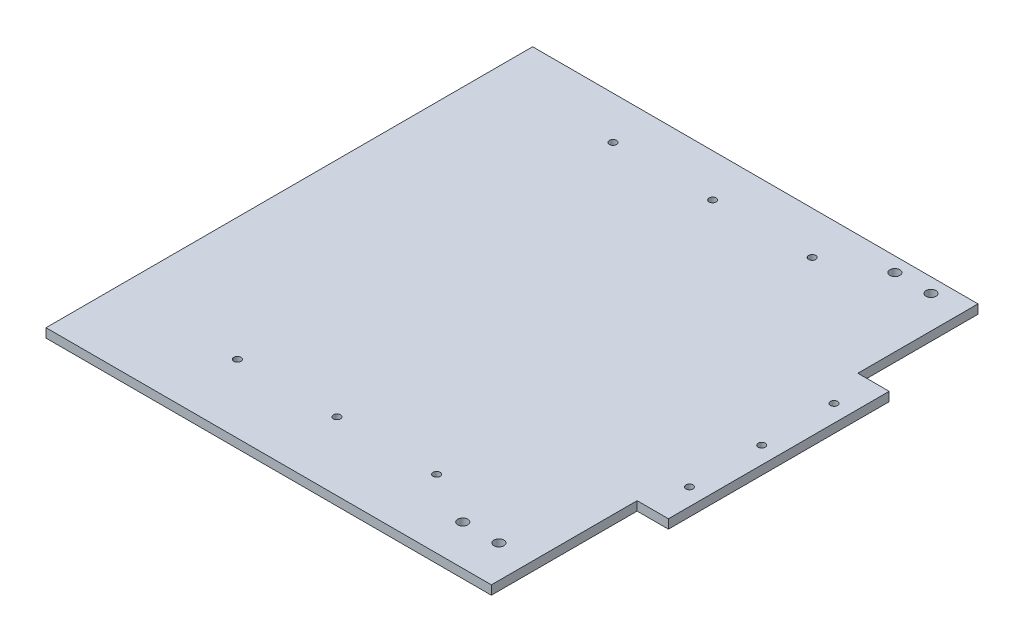
SolidWorks part; units mm, degrees
material "Cedar"
ref_plane "Front Plane" through (0, 0, 0) normal (0, 0, 1) x (1, 0, 0)
ref_plane "Top Plane" through (0, 0, 0) normal (0, 1, 0) x (1, 0, 0)
ref_plane "Right Plane" through (0, 0, 0) normal (1, 0, 0) x (0, 0, -1)
sketch "Sketch1" plane through (0, 0, 0) normal (0, 1, 0) x (1, 0, 0)
  line L0 (72.8376, -16.2766) -> (72.8376, -52.4668) construction
  line L1 (-156.5, -171) -> (156.5, -171)
  line L2 (-156.5, -171) -> (-156.5, 171)
  line L3 (-156.5, 171) -> (156.5, 171)
  line L4 (156.5, -171) -> (156.5, 171)
  line L5 (-156.5, -171) -> (156.5, 171) construction
  line L6 (-156.5, 171) -> (156.5, -171) construction
  point P0 (0, 0)
  dimension "D1" = 342
  dimension "D2" = 313
extrude "Boss-Extrude1" add sketch "Sketch1" against normal blind 6.35
ref_plane "Plane1" through (0, 0, -9) normal (0, 0, -1) x (-1, 0, 0)
sketch "Sketch3" plane through (0, 0, 0) normal (0, 1, 0) x (1, 0, 0)
  line L0 (156.5, 9) -> (-156.5, 9) construction
  line L1 (156.5, -171) -> (156.5, 171) construction
  line L2 (-156.5, 171) -> (-156.5, -171) construction
  line L3 (55, 9) -> (-55, 9) construction
  line L4 (156.5, 86.5702) -> (156.5, -68.5702)
  line L5 (156.5, -68.5702) -> (178.5, -68.5702)
  line L6 (178.5, -68.5702) -> (178.5, 86.5702)
  line L7 (178.5, 86.5702) -> (156.5, 86.5702)
  line L8 (166.5, 59.8) -> (166.5, 9) construction
  circle A0 centre (166.5, 9) radius 2.5
  circle A1 centre (166.5, -41.8) radius 2.5
  circle A2 centre (166.5, 59.8) radius 2.5
  point P10 (156.5, 9)
  dimension "D2" = 5
  dimension "D4" = 5
  dimension "D5" = 50.8
  dimension "D1" = 22
  dimension "D3" = 10
  dimension "D6" = 0
extrude "Boss-Extrude2" add sketch "Sketch3" against normal blind 6.35
sketch "Sketch2" plane through (0, 0, 0) normal (0, 1, 0) x (1, 0, 0)
  line L0 (156.5, 9) -> (-156.5, 9) construction
  line L1 (156.5, -171) -> (156.5, -68.5702) construction
  line L2 (-156.5, 171) -> (-156.5, -171) construction
  line L3 (0, -123) -> (0, -171) construction
  line L4 (55, 9) -> (-55, 9) construction
  line L5 (156.5, -123) -> (-156.5, -123) construction
  line L6 (-156.5, -171) -> (156.5, -171) construction
  circle A0 centre (0, -123) radius 2.5
  circle A1 centre (-70, -123) radius 2.5
  circle A2 centre (70, -123) radius 2.5
  circle A3 centre (-70, 141) radius 2.5
  circle A4 centre (0, 141) radius 2.5
  circle A5 centre (70, 141) radius 2.5
  dimension "D2" = 5
  dimension "D3" = 5
  dimension "D4" = 70
  dimension "D1" = 132
extrude "Cut-Extrude1" cut sketch "Sketch2" against normal through all
sketch "Sketch4" plane through (0, 0, 0) normal (0, 1, 0) x (1, 0, 0)
  line L0 (156.5, -171) -> (156.5, -68.5702) construction
  line L1 (108.24, -142.84) -> (133.64, -142.84) construction
  line L2 (-156.5, -171) -> (156.5, -171) construction
  circle A0 centre (133.64, -142.84) radius 3.5
  circle A1 centre (108.24, -142.84) radius 3.5
  dimension "D1" = 7
  dimension "D2" = 7
  dimension "D3" = 25.4
  dimension "D4" = 22.86
  dimension "D5" = 28.16
extrude "Cut-Extrude2" cut sketch "Sketch4" against normal through all
mirror "Mirror1" about plane through (0, 0, -9) normal (0, 0, -1) of "Cut-Extrude2"
